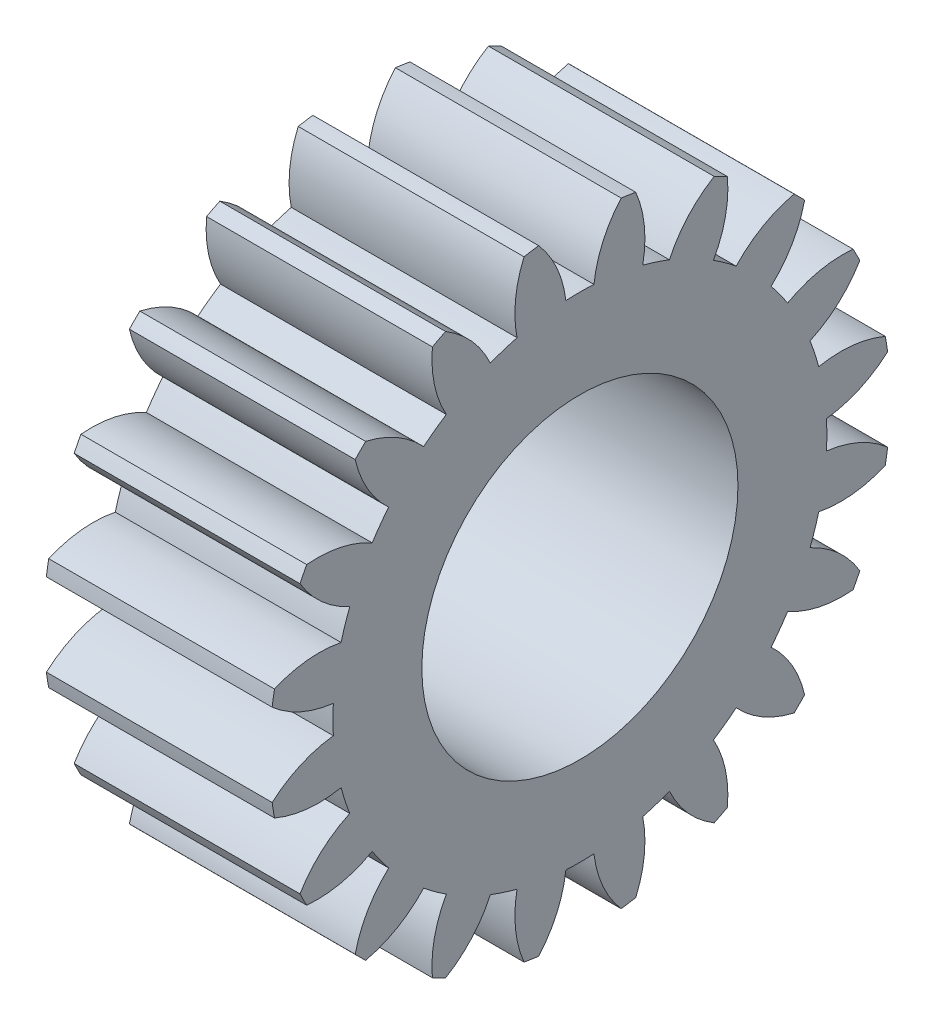
SolidWorks part; units mm, degrees
ref_plane "Plane1" through (0, 0, 0) normal (0, 0, 1) x (1, 0, 0)
ref_plane "Plane2" through (0, 0, 0) normal (0, 1, 0) x (1, 0, 0)
ref_plane "Plane3" through (0, 0, 0) normal (1, 0, 0) x (0, 0, -1)
sketch "HoldingSke" plane through (0, 0, 0) normal (0, 1, 0) x (1, 0, 0)
  line L0 (0, 0) -> (0.7518, -0.2736)
  line L1 (-15, 0) -> (100, 0) construction
  line L2 (0, 0) -> (-2.1039, 2.3779)
  line L3 (0, 0) -> (-11.863, 4.5341)
  line L4 (0, 0) -> (8.1152, 2.9537)
  line L5 (0, 0) -> (-46.8476, -17.4728)
  line L6 (0, 0) -> (-8.2896, -5.593)
  line L7 (-2.1039, 2.3779) -> (8.6586, 51.2059)
  line L8 (-76.2, 54.61) -> (-73.9, 54.61)
  line L9 (-71.009, 38.7566) -> (-53.1078, 45.2721)
  line L10 (-76.2, 71.12) -> (104.1128, 71.12)
  line L11 (0, 0) -> (-10, 0)
  line L12 (-76.2, 101.6) -> (-76.155, 101.6)
  line L13 (24.9733, 27.94) -> (52.9518, 28.4284)
  line L14 (24.9733, 27.94) -> (24.9743, 27.94)
  line L15 (24.9733, 27.94) -> (100.4006, 29.5858)
  line L16 (-63.627, -1.25) -> (-12.827, -1.25)
  circle A0 centre (0, 0) radius 7
  circle A1 centre (0, 0) radius 10.9365
  circle A2 centre (0, 0) radius 37.5
  circle A3 centre (0, 0) radius 7
  dimension "Num_teeth" = 20
  dimension "Pitch_radius" = 180.3128
  dimension "Width" = 10
  dimension "Thickness" = 10
sketch "BasProSke" plane through (0, 0, 0) normal (0, 1, 0) x (1, 0, 0)
  line L0 (-10, 0) -> (60, 0) construction
  line L1 (0, 0) -> (0, 13.75)
  line L2 (0, 0) -> (10, 0)
  line L3 (10, 0) -> (10, 13.75)
  line L4 (10, 13.75) -> (0, 13.75)
  dimension "Thickness" = 10
  dimension "Diameter" = 27.5
revolve "Base-Revolve" add sketch "BasProSke" angle 360 about L0
sketch "TooCutSke" plane through (0, 0, 0) normal (1, 0, 0) x (0, 0, -1)
  line L1 (0, 0) -> (0, 107) construction
  line L2 (0, 0) -> (-1.0594, 12.455) construction
  line L3 (0, 0) -> (-3.9007, 24.6278) construction
  line L4 (-1.0594, 12.455) -> (-1.9503, 12.3139) construction
  arc A0 (0.6211, 10.9188) -> (-0.6211, 10.9188) centre (0, 0) ccw
  arc A1 (1.8466, 13.6511) -> (-1.8466, 13.6511) centre (0, 0) ccw
  circle A2 centre (0, 0) radius 12.5 construction
  circle A3 centre (0, 0) radius 11.7462 construction
  arc A4 (-0.6211, 10.9188) -> (-1.8466, 13.6511) centre (-5.5866, 10.3326) ccw
  arc A5 (1.8466, 13.6511) -> (0.6211, 10.9188) centre (5.5866, 10.3326) ccw
extrude "ToothCut" cut sketch "TooCutSke" along normal through all
fillet "Breaks" [suppressed] radius 0.025 tangent propagation no
fillet "RootFillets" [suppressed] radius 0.3135
pattern_circular "TeethCuts" count 20 every 18 about axis through (-10, 0, 0) along (1, 0, 0) of "ToothCut", "RootFillets", "Breaks"
sketch "HubNeaOneSke" plane through (0, 0, 0) normal (-1, 0, 0) x (0, 0, 1)
  circle A0 centre (0, 0) radius 10.9365
  dimension "Diameter" = 21.873
extrude "HubNearOne" [suppressed] add sketch "HubNeaOneSke" along normal blind 40.0001
sketch "HubNeaBotSke" plane through (0, 0, 0) normal (-1, 0, 0) x (0, 0, 1)
  circle A0 centre (0, 0) radius 10.9365
  dimension "Diameter" = 21.873
extrude "HubNearBoth" [suppressed] add sketch "HubNeaBotSke" along normal blind 20
ref_plane "FarPln" through (10, 0, 0) normal (1, 0, 0) x (0, 0, -1)
sketch "HubFarSke" plane through (10, 0, 0) normal (1, 0, 0) x (0, 0, -1)
  circle A0 centre (0, 0) radius 10.9365
  dimension "Diameter" = 21.873
extrude "HubFar" [suppressed] add sketch "HubFarSke" along normal blind 20
sketch "BorSke" plane through (0, 0, 0) normal (1, 0, 0) x (0, 0, -1)
  circle A0 centre (0, 0) radius 7
  dimension "Diameter" = 14
extrude "Bore" cut sketch "BorSke" along normal mid plane 100.0001
sketch "KeySke" plane through (0, 0, 0) normal (1, 0, 0) x (0, 0, -1)
  line L0 (-2.5, 0) -> (-2.5, 9.3)
  line L1 (-2.5, 9.3) -> (2.5, 9.3)
  line L2 (2.5, 9.3) -> (2.5, 0)
  line L3 (0, 0) -> (0, 34) construction
  line L4 (-2.5, 0) -> (2.5, 0)
  dimension "Width" = 5
extrude "Keyway" [suppressed] cut sketch "KeySke" along normal mid plane 100.0001
pattern_circular "Keyway2" [suppressed] count 2 every 90 about axis through (-10, 0, 0) along (1, 0, 0) reverse direction yes
sketch "Sketch1" plane through (10, 0, 0) normal (1, 0, 0) x (0, 0, -1)
equation "' \"Module@HoldingSke\" = 6.35"
equation "' \"Num_teeth@HoldingSke\" = 12"
equation "' \"Ap@HoldingSke\" =  20"
equation "' \"Ap@HoldingSke\" = 20"
equation "' \"Width@HoldingSke\" = 0.5 * 25.4"
equation "' \"Hub_dia@HoldingSke\"= 1 * 25.4"
equation "' \"Hub_dia@HoldingSke\" = 1 * 25.4"
equation "' \"Overall_len@HoldingSke\" = 1.0 * 25.4"
equation "' \"Bore@HoldingSke\" = 0.75 * 25.4"
equation "' \"T_dim@HoldingSke\" = 0.1 * 25.4"
equation "' \"Width@KeySke\" = 0.25 * 25.4"
equation "' \"Show_teeth@HoldingSke\" = 13"
equation "' \"Backlash@HoldingSke\" = 0.009 * 25.4"
equation "' \"Addendum_fac@HoldingSke\" = 1.0"
equation "' \"Dedendum_fac@HoldingSke\" = 1.25"
equation "' \"Dedendum_add@HoldingSke\" = 0.00005 * 25.4"
equation "' \"Clearance_fac@HoldingSke\" = 0.25"
equation "\"Pitch@HoldingSke\" = 1 / \"Module@HoldingSke\""
equation "\"Overcut_dia@TooCutSke\" = (\"Num_teeth@HoldingSke\" + 2 * \"Addendum_fac@HoldingSke\") / \"Pitch@HoldingSke\" + 0.002 * 25.4"
equation "\"Pitch_dia@TooCutSke\" = \"Num_teeth@HoldingSke\" / \"Pitch@HoldingSke\""
equation "\"Base_dia@TooCutSke\" = \"Num_teeth@HoldingSke\" / \"Pitch@HoldingSke\" * cos((\"Ap@HoldingSke\"  * 3.14159265 / 180))"
equation "\"Root_dia@TooCutSke\" = (\"Num_teeth@HoldingSke\" + 2) / \"Pitch@HoldingSke\" - 2 * (\"Addendum_fac@HoldingSke\" + \"Dedendum_fac@HoldingSke\") / \"Pitch@HoldingSke\" - \"Dedendum_add@HoldingSke\" * 2"
equation "\"Half_ang@TooCutSke\" = 180 / \"Num_teeth@HoldingSke\""
equation "\"Half_CT@TooCutSke\" = \"Num_teeth@HoldingSke\" / \"Pitch@HoldingSke\" * sin((3.14159265 / 2 / \"Num_teeth@HoldingSke\")) / 2 - 7 * \"Backlash@HoldingSke\" / 4"
equation "\"Flank_rad@TooCutSke\" = \"Num_teeth@HoldingSke\" / \"Pitch@HoldingSke\" / 5"
equation "\"Radius@RootFillets\" = \"Clearance_fac@HoldingSke\" / \"Pitch@HoldingSke\" + \"Dedendum_add@HoldingSke\""
equation "\"Break_rad@Breaks\" = 0.02 / \"Pitch@HoldingSke\""
equation "\"Thickness@HoldingSke\" = \"Width@HoldingSke\""
equation "\"OAL@HoldingSke\" = \"Thickness@HoldingSke\""
equation "\"MHD@HoldingSke\" = (\"Num_teeth@HoldingSke\" + 2) / \"Pitch@HoldingSke\" - 2 * (\"Addendum_fac@HoldingSke\" + \"Dedendum_fac@HoldingSke\")  / \"Pitch@HoldingSke\" - \"Dedendum_add@HoldingSke\" * 2"
equation "\"MBD@HoldingSke\" = (\"Num_teeth@HoldingSke\" + 2) / \"Pitch@HoldingSke\" - 2 * (\"Addendum_fac@HoldingSke\" + \"Dedendum_fac@HoldingSke\")  / \"Pitch@HoldingSke\" - \"Dedendum_add@HoldingSke\" * 2 - 0.002 * 25.4"
equation "\"MHD@HoldingSke\" = ((sgn( \"MHD@HoldingSke\" - \"Hub_dia@HoldingSke\" )-1)*( \"MHD@HoldingSke\" - \"Hub_dia@HoldingSke\" ))/-2+ \"Hub_dia@HoldingSke\""
equation "\"MBD@HoldingSke\" = ((sgn( \"MBD@HoldingSke\" - \"Bore@HoldingSke\" )-1)*( \"MBD@HoldingSke\" - \"Bore@HoldingSke\" ))/-2+ \"Bore@HoldingSke\""
equation "\"OAL@HoldingSke\" = ((sgn( \"OAL@HoldingSke\" - \"Overall_len@HoldingSke\" )+1)*( \"OAL@HoldingSke\" - \"Overall_len@HoldingSke\" ))/2 + \"Overall_len@HoldingSke\" + 0.000002 * 25.4"
equation "\"Num_teeth@TeethCuts\" = int( \"Show_teeth@HoldingSke\" ) + 1"
equation "\"Num_teeth@TeethCuts\" = ((sgn( \"Num_teeth@TeethCuts\" - \"Num_teeth@HoldingSke\" )-1)*( \"Num_teeth@TeethCuts\" - \"Num_teeth@HoldingSke\" ))/-2+ \"Num_teeth@HoldingSke\""
equation "\"Num_teeth@TeethCuts\" = ((sgn( \"Num_teeth@TeethCuts\" - 2.0)+1)*( \"Num_teeth@TeethCuts\" - 2.0))/2 +2.0"
equation "\"Angle@TeethCuts\" = 360.0 / \"Num_teeth@HoldingSke\""
equation "\"Diameter@BasProSke\" = (\"Num_teeth@HoldingSke\" + 2 * \"Addendum_fac@HoldingSke\") / \"Pitch@HoldingSke\""
equation "\"Thickness@BasProSke\"  = \"Thickness@HoldingSke\""
equation "' \"Fillet_rad@BasProSke\" =  \"Thickness@HoldingSke\" * 0.05"
equation "' \"Fillet_rad@BasProSke\" = \"Thickness@HoldingSke\" * 0.05"
equation "\"MHD@HoldingSke\" = ((sgn( \"MHD@HoldingSke\" - \"Root_dia@TooCutSke\" )-1)*( \"MHD@HoldingSke\" - \"Root_dia@TooCutSke\" ))/-2+ \"Root_dia@TooCutSke\""
equation "\"Diameter@HubNeaOneSke\" = \"MHD@HoldingSke\""
equation "\"Length@HubNearOne\" = \"OAL@HoldingSke\" - \"Thickness@BasProSke\""
equation "\"Diameter@HubNeaBotSke\" = \"MHD@HoldingSke\""
equation "\"Length@HubNearBoth\" = ( \"OAL@HoldingSke\" - \"Thickness@BasProSke\" ) / 2.0"
equation "\"Thickness@FarPln\" = \"Thickness@BasProSke\""
equation "\"Diameter@HubFarSke\" = \"MHD@HoldingSke\""
equation "\"Length@HubFar\" = ( \"OAL@HoldingSke\" - \"Thickness@BasProSke\" ) / 2.0"
equation "\"Diameter@BorSke\" = \"MBD@HoldingSke\""
equation "\"D1@Bore\" = \"OAL@HoldingSke\" * 2.0"
equation "\"D1@Keyway\" = \"OAL@HoldingSke\" * 2.0"
equation "\"Offset@KeySke\" = \"T_dim@HoldingSke\" + \"MBD@HoldingSke\" / 2.0"
